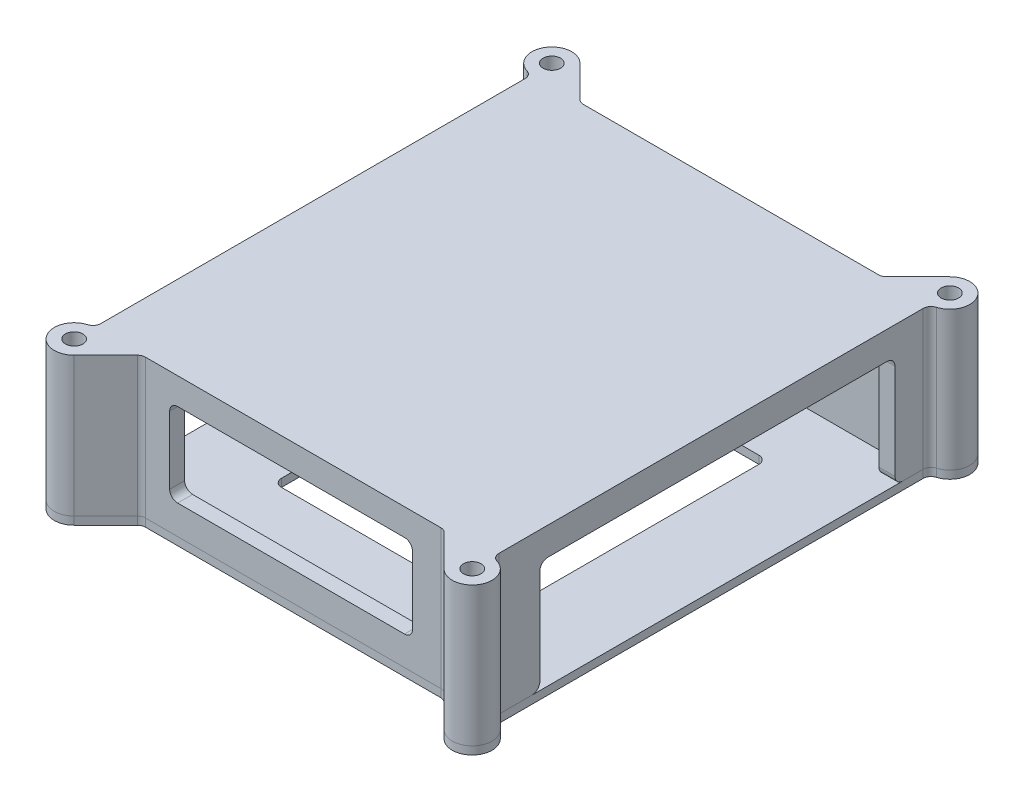
SolidWorks part; units mm, degrees
material "Nylon 101"
ref_plane "Front Plane" through (0, 0, 0) normal (0, 0, 1) x (1, 0, 0)
ref_plane "Top Plane" through (0, 0, 0) normal (0, 1, 0) x (1, 0, 0)
ref_plane "Right Plane" through (0, 0, 0) normal (1, 0, 0) x (0, 0, -1)
sketch "Sketch1" plane through (0, 0, 0) normal (0, 1, 0) x (1, 0, 0)
  line L1 (0, 0) -> (127, 0)
  line L2 (0, 0) -> (0, 139.7)
  line L3 (0, 139.7) -> (127, 139.7)
  line L4 (127, 0) -> (127, 139.7)
  dimension "D1" = 127
  dimension "D2" = 139.7
extrude "Boss-Extrude1" add sketch "Sketch1" along normal blind 44.45
sketch "Sketch3" plane through (0, 0, 0) normal (0, -1, 0) x (1, 0, 0)
  line L0 (0, -139.7) -> (0, 0) construction
  line L1 (6.35, -4.7625) -> (121.92, -4.7625)
  line L2 (6.35, -4.7625) -> (6.35, -135.8265)
  line L3 (6.35, -135.8265) -> (121.92, -135.8265)
  line L4 (121.92, -4.7625) -> (121.92, -135.8265)
  line L5 (0, 0) -> (127, 0) construction
  dimension "D1" = 115.57
  dimension "D2" = 131.064
  dimension "D3" = 6.35
  dimension "D4" = 4.7625
extrude "Cut-Extrude1" cut sketch "Sketch3" against normal blind 44
sketch "Sketch4" plane through (0, 0, -139.7) normal (0, 0, -1) x (-1, 0, 0)
  line L0 (-127, 0) -> (0, 0) construction
  line L1 (-101.6, 35.941) -> (-24.13, 35.941)
  line L2 (-101.6, 35.941) -> (-101.6, 9.271)
  line L3 (-101.6, 9.271) -> (-24.13, 9.271)
  line L4 (-24.13, 35.941) -> (-24.13, 9.271)
  line L7 (-127, 44.45) -> (-127, 0) construction
  dimension "D1" = 26.67
  dimension "D2" = 77.47
  dimension "D3" = 9.271
  dimension "D4" = 25.4
extrude "Cut-Extrude2" cut sketch "Sketch4" against normal blind 190.754
sketch "Sketch5" plane through (127, 0, 0) normal (1, 0, 0) x (0, 0, -1)
  line L0 (0, 44.45) -> (139.7, 44.45) construction
  line L1 (15.24, 35.56) -> (128.524, 35.56)
  line L2 (15.24, 35.56) -> (15.24, -11.43)
  line L3 (15.24, -11.43) -> (128.524, -11.43)
  line L4 (128.524, 35.56) -> (128.524, -11.43)
  line L6 (0, 44.45) -> (0, 0) construction
  dimension "D1" = 46.99
  dimension "D2" = 113.284
  dimension "D3" = 8.89
  dimension "D4" = 15.24
extrude "Cut-Extrude3" cut sketch "Sketch5" against normal blind 190.754 contours L2 L1 L4 L3
sketch "Sketch6" plane through (0, 0, 0) normal (0, -1, 0) x (-1, 0, 0)
  line L6 (0, 0) -> (-127, 0) construction
  line L7 (-127, 146.05) -> (0, 146.05) construction
  line L8 (-127, 146.05) -> (-127, -6.35) construction
  line L9 (-127, -6.35) -> (0, -6.35) construction
  line L10 (0, 146.05) -> (0, -6.35) construction
  line L12 (-122.5099, 150.5401) -> (-111.6697, 139.7)
  line L13 (-127, 139.7) -> (0, 139.7) construction
  line L14 (-4.4901, 150.5401) -> (-15.3303, 139.7)
  line L15 (-4.4901, -10.8401) -> (-15.3303, 0)
  line L16 (-122.5099, -10.8401) -> (-111.6697, 0)
  line L17 (-127, 0) -> (-111.6697, 0)
  line L18 (-15.3303, 0) -> (0, 0)
  line L19 (-127, 0) -> (-127, 15.24) construction
  line L20 (-127, 139.7) -> (0, 139.7)
  circle A0 centre (0, -6.35) radius 2.794
  circle A1 centre (-127, -6.35) radius 2.794
  circle A2 centre (0, 146.05) radius 2.794
  circle A3 centre (-127, 146.05) radius 2.794
  circle A4 centre (-127, -6.35) radius 6.35
  circle A5 centre (0, -6.35) radius 6.35
  circle A6 centre (0, 146.05) radius 6.35
  circle A7 centre (-127, 146.05) radius 6.35
  line M3 (-127, 0) -> (0, 0)
  dimension "D1" = 5.588
  dimension "D2" = 5.588
  dimension "D3" = 5.588
  dimension "D4" = 5.588
  dimension "D6" = 152.4
  dimension "D5" = 127
ref_plane "Plane1" through (63.5, 0, 0) normal (1, 0, 0) x (0, 0, -1)
ref_plane "Plane4" through (0, 0, -69.85) normal (0, 0, -1) x (-1, 0, 0)
extrude "Boss-Extrude2" add sketch "Sketch6" against normal through all contours A7 A3 | A7 L20 L12 | A6 L14 L20 | A4 A1 | A4 L16 M3 | A5 L15 M3 | A5 A0 | A6 A2 region at (8.5187, 0, -142.5214) region at (118.4813, 0, -142.5214) region at (121.2993, 0, -148.4113) region at (-2.3613, 0, -151.7507) region at (118.4813, 0, 2.8214) region at (8.5187, 0, 2.8214) region at (5.7007, 0, 3.9887) region at (132.7007, 0, 8.7113)
fillet "Fillet1" radius 2.54 24 edges at (0, 22.225, -139.7) (15.3303, 22.225, -139.7) (127, 22.225, -139.7) (127, 22.225, 0) (111.6697, 22.225, 0) (15.3303, 22.225, 0) (0, 22.225, 0) (111.6697, 22.225, -139.7) (24.13, 9.271, -2.3813) (101.6, 9.271, -2.3813) (101.6, 35.941, -2.3813) (24.13, 35.941, -2.3813) (24.13, 9.271, -137.7632) (101.6, 9.271, -137.7632) (101.6, 35.941, -137.7632) (24.13, 35.941, -137.7632) (3.175, 0, -128.524) (3.175, 0, -15.24) (124.46, 0, -15.24) (124.46, 0, -128.524) (3.175, 35.56, -128.524) (124.46, 35.56, -15.24) (3.175, 35.56, -15.24) (124.46, 35.56, -128.524)
sketch "Sketch7" plane through (0, 0, 0) normal (0, -1, 0) x (1, 0, 0)
  line L1 (127, -12.7) -> (127, -2.1694) construction
  line L2 (122.5099, 10.8401) -> (112.4137, 0.7439) construction
  line L3 (110.6176, 0) -> (16.3824, 0) construction
  line L4 (14.5863, 0.7439) -> (4.4901, 10.8401) construction
  line L5 (0, -2.1694) -> (0, -12.7) construction
  line L10 (127, -137.5306) -> (127, -131.064) construction
  line L16 (0, -131.064) -> (0, -137.5306) construction
  line L17 (4.4901, -150.5401) -> (14.5863, -140.4439) construction
  line L18 (16.3824, -139.7) -> (110.6176, -139.7) construction
  line L19 (112.4137, -140.4439) -> (122.5099, -150.5401) construction
  line L21 (127, -12.7) -> (127, -2.1694)
  line L22 (122.5099, 10.8401) -> (112.4137, 0.7439)
  line L23 (110.6176, 0) -> (16.3824, 0)
  line L24 (14.5863, 0.7439) -> (4.4901, 10.8401)
  line L25 (0, -2.1694) -> (0, -12.7)
  line L30 (127, -137.5306) -> (127, -131.064)
  line L36 (0, -131.064) -> (0, -137.5306)
  line L37 (4.4901, -150.5401) -> (14.5863, -140.4439)
  line L38 (16.3824, -139.7) -> (110.6176, -139.7)
  line L39 (112.4137, -140.4439) -> (122.5099, -150.5401)
  line L40 (0, -131.064) -> (0, -12.7)
  line L41 (127, -12.7) -> (127, -131.064)
  line L43 (27.1096, -30.1617) -> (99.4355, -30.1617)
  line L44 (27.1096, -30.1617) -> (27.1096, -115.2243)
  line L45 (27.1096, -115.2243) -> (99.4355, -115.2243)
  line L46 (99.4355, -30.1617) -> (99.4355, -115.2243)
  circle A0 centre (127, -146.05) radius 2.794 construction
  circle A1 centre (0, -146.05) radius 2.794 construction
  circle A2 centre (127, 6.35) radius 2.794 construction
  circle A3 centre (0, 6.35) radius 2.794 construction
  circle A4 centre (127, -146.05) radius 2.794
  circle A5 centre (0, -146.05) radius 2.794
  circle A6 centre (127, 6.35) radius 2.794
  circle A7 centre (0, 6.35) radius 2.794
  arc A8 (128.8143, 0.2647) -> (127, -2.1694) centre (129.54, -2.1694) ccw construction
  arc A9 (128.8143, 0.2647) -> (122.5099, 10.8401) centre (127, 6.35) ccw construction
  arc A10 (110.6176, 0) -> (112.4137, 0.7439) centre (110.6176, 2.54) ccw construction
  arc A11 (14.5863, 0.7439) -> (16.3824, 0) centre (16.3824, 2.54) ccw construction
  arc A12 (4.4901, 10.8401) -> (-1.8143, 0.2647) centre (0, 6.35) ccw construction
  arc A13 (0, -2.1694) -> (-1.8143, 0.2647) centre (-2.54, -2.1694) ccw construction
  arc A14 (-1.8143, -139.9647) -> (0, -137.5306) centre (-2.54, -137.5306) ccw construction
  arc A15 (-1.8143, -139.9647) -> (4.4901, -150.5401) centre (0, -146.05) ccw construction
  arc A16 (16.3824, -139.7) -> (14.5863, -140.4439) centre (16.3824, -142.24) ccw construction
  arc A17 (112.4137, -140.4439) -> (110.6176, -139.7) centre (110.6176, -142.24) ccw construction
  arc A18 (122.5099, -150.5401) -> (128.8143, -139.9647) centre (127, -146.05) ccw construction
  arc A19 (127, -137.5306) -> (128.8143, -139.9647) centre (129.54, -137.5306) ccw construction
  arc A20 (128.8143, 0.2647) -> (127, -2.1694) centre (129.54, -2.1694) ccw
  arc A21 (128.8143, 0.2647) -> (122.5099, 10.8401) centre (127, 6.35) ccw
  arc A22 (110.6176, 0) -> (112.4137, 0.7439) centre (110.6176, 2.54) ccw
  arc A23 (14.5863, 0.7439) -> (16.3824, 0) centre (16.3824, 2.54) ccw
  arc A24 (4.4901, 10.8401) -> (-1.8143, 0.2647) centre (0, 6.35) ccw
  arc A25 (0, -2.1694) -> (-1.8143, 0.2647) centre (-2.54, -2.1694) ccw
  arc A26 (-1.8143, -139.9647) -> (0, -137.5306) centre (-2.54, -137.5306) ccw
  arc A27 (-1.8143, -139.9647) -> (4.4901, -150.5401) centre (0, -146.05) ccw
  arc A28 (16.3824, -139.7) -> (14.5863, -140.4439) centre (16.3824, -142.24) ccw
  arc A29 (112.4137, -140.4439) -> (110.6176, -139.7) centre (110.6176, -142.24) ccw
  arc A30 (122.5099, -150.5401) -> (128.8143, -139.9647) centre (127, -146.05) ccw
  arc A31 (127, -137.5306) -> (128.8143, -139.9647) centre (129.54, -137.5306) ccw
extrude "Boss-Extrude3" add sketch "Sketch7" along normal blind 2.54 separate body
fillet "Fillet2" radius 2.54 4 edges at (99.4355, -1.27, -115.2243) (99.4355, -1.27, -30.1617) (27.1096, -1.27, -115.2243) (27.1096, -1.27, -30.1617)
